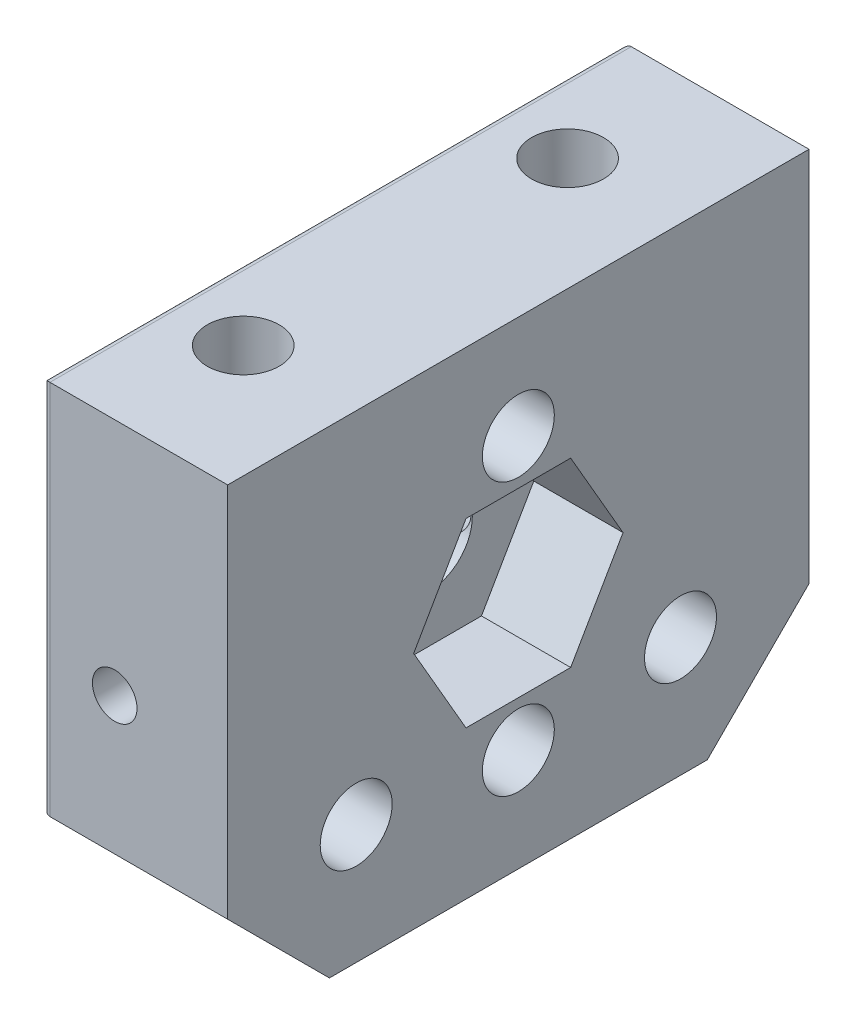
SolidWorks part; units mm, degrees
ref_plane "Płaszczyzna przednia" through (0, 0, 0) normal (0, 0, 1) x (1, 0, 0)
ref_plane "Płaszczyzna górna" through (0, 0, 0) normal (0, 1, 0) x (1, 0, 0)
ref_plane "Płaszczyzna prawa" through (0, 0, 0) normal (1, 0, 0) x (0, 0, -1)
sketch "Szkic1" plane through (0, 0, 0) normal (1, 0, 0) x (0, 0, -1)
  line L1 (-20.1998, -16.6055) -> (20.1998, -16.6055)
  line L2 (-20.1998, -16.6055) -> (-20.1998, 16.6055)
  line L3 (-20.1998, 16.6055) -> (20.1998, 16.6055)
  line L4 (20.1998, -16.6055) -> (20.1998, 16.6055)
  line L5 (-20.1998, -16.6055) -> (20.1998, 16.6055) construction
  line L6 (-20.1998, 16.6055) -> (20.1998, -16.6055) construction
  circle A0 centre (0, 0) radius 3
  point P0 (0, 0)
  dimension "D1" = 6
extrude "Dodanie-wyciągnięcie1" add sketch "Szkic1" along normal blind 10
sketch "Szkic2" plane through (0, 0, 20.1998) normal (0, 0, 1) x (1, 0, 0)
  line L1 (0, 16.6055) -> (0, -16.6055) construction
  line L2 (0, 0) -> (16.3925, 0) construction
  line L3 (10, 16.6055) -> (0, 16.6055) construction
  line L4 (5, 16.6055) -> (5, -8.9167) construction
  circle A0 centre (5, 0) radius 1.55
  dimension "D1" = 3.1
extrude "Wytnij-wyciągnięcie1" cut sketch "Szkic2" against normal through all both and the other way through all
sketch "Szkic4" plane through (0, 0, 0) normal (-1, 0, 0) x (0, 0, 1)
  circle A0 centre (0, 0) radius 6.65
  dimension "D1" = 13.3
extrude "Wytnij-wyciągnięcie2" cut sketch "Szkic4" against normal blind 3
ref_plane "Płaszczyzna1" through (0, 8.3027, 0) normal (0, 1, 0) x (1, 0, 0)
sketch "Szkic5" plane through (0, 8.3027, 0) normal (0, 1, 0) x (1, 0, 0)
  line L0 (10, 20.1998) -> (10, -20.1998) construction
  line L1 (9, -13.5782) -> (9, -8.9594)
  line L2 (9, -8.9594) -> (5, -6.65)
  line L3 (5, -6.65) -> (1, -8.9594)
  line L4 (1, -8.9594) -> (1, -13.5782)
  line L5 (1, -13.5782) -> (5, -15.8876)
  line L6 (5, -15.8876) -> (9, -13.5782)
  line L7 (3, 6.65) -> (3, -6.65) construction
  line L8 (3, 6.65) -> (3, -6.65) construction
  line L9 (3, -6.65) -> (14.7552, -6.65) construction
  line L10 (10, -20.1998) -> (0, -20.1998) construction
  line L11 (10, -20.1998) -> (0, -20.1998) construction
  line L12 (5, -20.1998) -> (5, -12.2172) construction
  circle A0 centre (5, -11.2688) radius 4 construction
  dimension "D1" = 8
extrude "Wytnij-wyciągnięcie3" cut sketch "Szkic5" against normal mid plane 4
sketch "Szkic6" plane through (0, 0, 0) normal (-1, 0, 0) x (0, 0, 1)
  line L0 (6.65, 6.3027) -> (6.65, 10.3027) construction
  line L1 (15.8876, 6.3027) -> (15.8876, 10.3027) construction
  line L2 (6.65, 6.3027) -> (6.65, 10.3027)
  line L3 (15.8876, 6.3027) -> (15.8876, 10.3027)
  line L4 (15.8876, 10.3027) -> (6.65, 10.3027)
  line L5 (6.65, 6.3027) -> (15.8876, 6.3027)
extrude "Wytnij-wyciągnięcie6" cut sketch "Szkic6" against normal up to next
ref_plane "Płaszczyzna2" through (0, 0, 0) normal (0, -1, 0) x (-1, 0, 0)
sketch "Szkic7" plane through (0, 16.6055, 0) normal (0, 1, 0) x (1, 0, 0)
  line L0 (5, -6.65) -> (5, -15.8876) construction
  line L6 (0, -15.8876) -> (5, -15.8876)
  line L7 (5, -15.8876) -> (9, -13.5782)
  line L8 (9, -13.5782) -> (9, -8.9594)
  line L9 (9, -8.9594) -> (5, -6.65)
  line L10 (5, -6.65) -> (0, -6.65)
  line L11 (0, -6.65) -> (0, -15.8876)
  line L12 (0, -15.8876) -> (5, -15.8876) construction
  line L13 (5, -15.8876) -> (9, -13.5782) construction
  line L14 (9, -13.5782) -> (9, -8.9594) construction
  line L15 (9, -8.9594) -> (5, -6.65) construction
  line L16 (5, -6.65) -> (0, -6.65) construction
  line L17 (0, -6.65) -> (0, -15.8876) construction
  circle A0 centre (5, -11.2688) radius 2.5
  dimension "D2" = 5
  dimension "D1" = 0
extrude "Wytnij-wyciągnięcie7" cut sketch "Szkic7" against normal up to surface (16.6055 mm away) up to plane "Płaszczyzna2"
sketch "Szkic8" plane through (0, 0, 0) normal (-1, 0, 0) x (0, 0, 1)
  line L2 (0, 0) -> (0, -16.6055) construction
  line L3 (20.1998, -16.6055) -> (-20.1998, -16.6055) construction
  line L4 (20.1998, -16.6055) -> (-20.1998, -16.6055) construction
  line L5 (20.1998, -16.6055) -> (20.1998, 0) construction
  line L6 (20.1998, 16.6055) -> (20.1998, -16.6055) construction
  line L7 (0, -8.3027) -> (22.8152, -8.3027) construction
  line L9 (8.7688, 10.3027) -> (13.7688, 10.3027) construction
  line L10 (8.7688, 10.3027) -> (13.7688, 10.3027) construction
  line L11 (11.2688, 10.3027) -> (11.2688, -12.6359) construction
  circle A0 centre (11.2688, -8.3027) radius 5.25
  dimension "D1" = 10.5
extrude "Wytnij-wyciągnięcie8" cut sketch "Szkic8" against normal blind 6
sketch "Szkic9" plane through (6, 0, 0) normal (-1, 0, 0) x (0, 0, 1)
  circle A0 centre (11.2688, -8.3027) radius 2.5
  dimension "D1" = 5
extrude "Wytnij-wyciągnięcie9" cut sketch "Szkic9" against normal through all
sketch "Szkic10" plane through (0, 0, 0) normal (-1, 0, 0) x (0, 0, 1)
  line L0 (13.1287, -16.6055) -> (20.1998, -9.5344)
  line L1 (20.1998, -16.6055) -> (-20.1998, -16.6055) construction
  line L2 (20.1998, 16.6055) -> (20.1998, -16.6055) construction
  line L3 (20.1998, -9.5344) -> (20.1998, -16.6055)
  line L4 (20.1998, -16.6055) -> (13.1287, -16.6055)
  dimension "D1" = 45
  dimension "D2" = 10
extrude "Wytnij-wyciągnięcie10" cut sketch "Szkic10" against normal through all
mirror "Lustro1" about plane through (0, 0, 0) normal (0, 0, 1) of "Wytnij-wyciągnięcie10", "Wytnij-wyciągnięcie9", "Wytnij-wyciągnięcie8", "Wytnij-wyciągnięcie6", "Wytnij-wyciągnięcie3", "Wytnij-wyciągnięcie7"
sketch "Szkic12" plane through (0, 0, 0) normal (-1, 0, 0) x (0, 0, 1)
  circle A0 centre (0, 9.4605) radius 2.5
  circle A1 centre (0, 9.4605) radius 5 construction
  dimension "D1" = 5
extrude "Wytnij-wyciągnięcie11" cut sketch "Szkic12" against normal through all
mirror "Lustro2" about plane through (0, 0, 0) normal (0, -1, 0) of "Wytnij-wyciągnięcie11"
fillet "Zaokrąglenie1" radius 0.5 19 edges at (0, 9.4605, 2.5) (0, 0, 6.65) (0, -9.4605, 2.5) (0, 16.6055, 0) (0, 3.5355, 20.1998) (0, -13.0699, 16.6643) (0, -16.6055, 0) (0, -13.0699, -16.6643) (0, 3.5355, -20.1998) (0, 10.3027, -11.2688) (0, 8.3027, -15.8876) (0, 6.3027, -11.2688) (0, 8.3027, -6.65) (0, 10.3027, 11.2688) (0, 8.3027, 6.65) (0, 6.3027, 11.2688) (0, 8.3027, 15.8876) (0, -8.3027, 16.5188) (0, -8.3027, -16.5188)
sketch "Szkic13" plane through (10, 0, 0) normal (1, 0, 0) x (0, 0, -1)
  line L6 (13.1287, -16.6055) -> (20.1998, -9.5344)
  line L7 (20.1998, -9.5344) -> (20.1998, 16.6055)
  line L8 (20.1998, 16.6055) -> (-20.1998, 16.6055)
  line L9 (-20.1998, 16.6055) -> (-20.1998, -9.5344)
  line L10 (-20.1998, -9.5344) -> (-13.1287, -16.6055)
  line L11 (-13.1287, -16.6055) -> (13.1287, -16.6055)
  line L12 (13.1287, -16.6055) -> (20.1998, -9.5344)
  line L13 (20.1998, -9.5344) -> (20.1998, 16.6055)
  line L14 (20.1998, 16.6055) -> (-20.1998, 16.6055)
  line L15 (-20.1998, 16.6055) -> (-20.1998, -9.5344)
  line L16 (-20.1998, -9.5344) -> (-13.1287, -16.6055)
  line L17 (-13.1287, -16.6055) -> (13.1287, -16.6055)
  circle A0 centre (-11.2688, -8.3027) radius 2.5 construction
  circle A1 centre (0, -9.4605) radius 2.5 construction
  circle A2 centre (11.2688, -8.3027) radius 2.5 construction
  circle A3 centre (0, 9.4605) radius 2.5 construction
  circle A4 centre (0, 0) radius 3 construction
  circle A5 centre (-11.2688, -8.3027) radius 2.5
  circle A6 centre (0, -9.4605) radius 2.5
  circle A7 centre (11.2688, -8.3027) radius 2.5
  circle A8 centre (0, 9.4605) radius 2.5
  circle A9 centre (0, 0) radius 3
  dimension "D1" = 0
extrude "Dodanie-wyciągnięcie2" add sketch "Szkic13" along normal blind 2.85
sketch "Szkic14" plane through (12.85, 0, 0) normal (1, 0, 0) x (0, 0, -1)
  line L0 (-13.1287, -16.6055) -> (13.1287, -16.6055) construction
  line L1 (3.6373, 6.3) -> (-3.6373, 6.3)
  line L2 (-3.6373, 6.3) -> (-7.2746, 0)
  line L3 (-7.2746, 0) -> (-3.6373, -6.3)
  line L4 (-3.6373, -6.3) -> (3.6373, -6.3)
  line L5 (3.6373, -6.3) -> (7.2746, 0)
  line L6 (7.2746, 0) -> (3.6373, 6.3)
  circle A0 centre (0, 0) radius 6.3 construction
  dimension "D1" = 12.6
extrude "Wytnij-wyciągnięcie12" cut sketch "Szkic14" against normal blind 6.2
